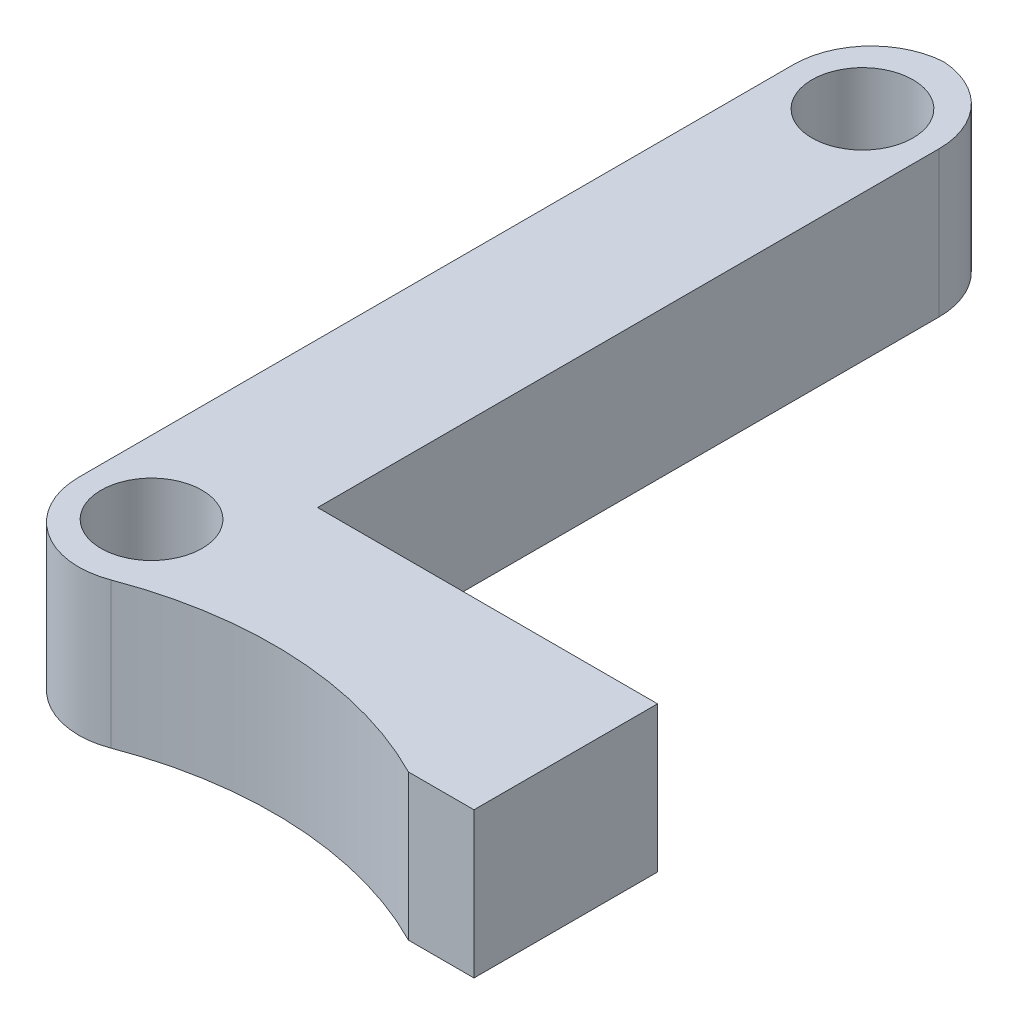
SolidWorks part; units mm, degrees
ref_plane "Front Plane" through (0, 0, 0) normal (0, 0, 1) x (1, 0, 0)
ref_plane "Top Plane" through (0, 0, 0) normal (0, 1, 0) x (1, 0, 0)
ref_plane "Right Plane" through (0, 0, 0) normal (1, 0, 0) x (0, 0, -1)
sketch "Sketch1" plane through (0, 0, 0) normal (0, 1, 0) x (1, 0, 0)
  line L0 (0, 23.241) -> (0, 0) construction
  line L1 (-4.7625, 28.575) -> (4.7625, 28.575)
  line L2 (-4.7625, 28.575) -> (-4.7625, -29.1465)
  line L4 (4.7625, 28.575) -> (4.7625, -17.145)
  line L7 (0, 0) -> (0, -23.241) construction
  line L26 (4.7625, -17.145) -> (26.9875, -17.145)
  line L27 (26.9875, -17.145) -> (26.9875, -29.1465)
  line L28 (-4.7625, -29.1465) -> (-0.4785, -29.1465)
  line L29 (26.9875, -29.1465) -> (22.7035, -29.1465)
  circle A0 centre (0, -23.241) radius 3.302
  circle A1 centre (0, 23.241) radius 3.302
  arc A6 (-0.4785, -29.1465) -> (22.7035, -29.1465) centre (11.1125, -51.7476) cw
  point P0 (0, 0)
  point P16 (0, 0)
  point P17 (0, 28.575)
  dimension "D3" = 6.604
  dimension "D5" = 25.4
  dimension "D4" = 9.525
  dimension "D9" = 23.182
  dimension "D1" = 31.75
  dimension "D2" = 46.482
  dimension "D6" = 45.72
  dimension "D7" = 57.7215
  dimension "D8" = 5.334
extrude "Boss-Extrude1" add sketch "Sketch1" along normal blind 9.525
fillet "Fillet1" radius 5.08 2 edges at (-4.7625, 4.7625, -28.575) (4.7625, 4.7625, -28.575)
fillet "Fillet2" radius 5.08 1 edges at (-4.7625, 4.7625, 29.1465)
fillet "Fillet3" radius 5.08 1 edges at (-0.4785, 4.7625, 29.1465)
